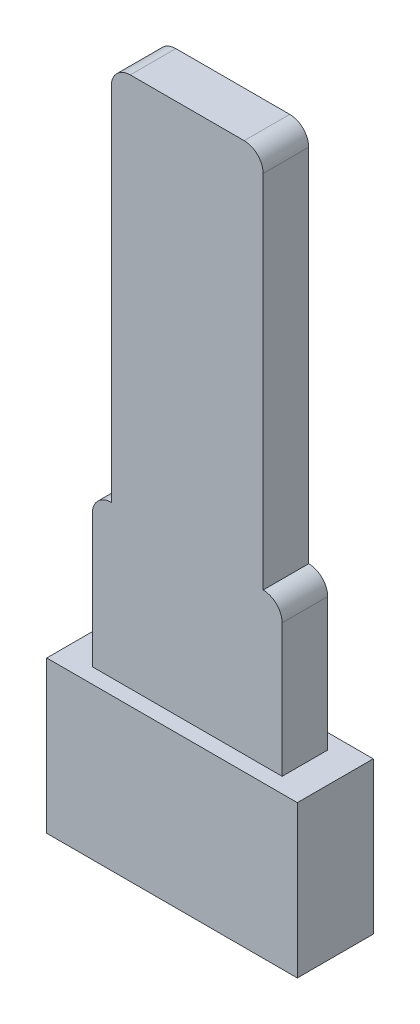
SolidWorks part; units mm, degrees
ref_plane "Front Plane" through (0, 0, 0) normal (0, 0, 1) x (1, 0, 0)
ref_plane "Top Plane" through (0, 0, 0) normal (0, 1, 0) x (1, 0, 0)
ref_plane "Right Plane" through (0, 0, 0) normal (1, 0, 0) x (0, 0, -1)
sketch "Sketch2" plane through (0, 0, 0) normal (0, 1, 0) x (1, 0, 0)
  line L1 (-3.3, -1) -> (3.3, -1)
  line L2 (-3.3, -1) -> (-3.3, 1)
  line L3 (-3.3, 1) -> (3.3, 1)
  line L4 (3.3, -1) -> (3.3, 1)
  line L5 (-3.3, -1) -> (3.3, 1) construction
  line L6 (-3.3, 1) -> (3.3, -1) construction
  point P0 (0, 0)
  dimension "D1" = 2
  dimension "D2" = 6.6
extrude "Boss-Extrude1" add sketch "Sketch2" along normal blind 4
sketch "Sketch3" plane through (0, 4, 0) normal (0, 1, 0) x (1, 0, 0)
  line L1 (-2.5, -0.6) -> (2.5, -0.6)
  line L2 (-2.5, -0.6) -> (-2.5, 0.6)
  line L3 (-2.5, 0.6) -> (2.5, 0.6)
  line L4 (2.5, -0.6) -> (2.5, 0.6)
  line L5 (-2.5, -0.6) -> (2.5, 0.6) construction
  line L6 (-2.5, 0.6) -> (2.5, -0.6) construction
  point P0 (0, 0)
  dimension "D1" = 5
  dimension "D2" = 1.2
extrude "Boss-Extrude2" add sketch "Sketch3" along normal blind 4
sketch "Sketch4" plane through (0, 8, 0) normal (0, 1, 0) x (1, 0, 0)
  line L1 (-2, -0.6) -> (2, -0.6)
  line L2 (-2, -0.6) -> (-2, 0.6)
  line L3 (-2, 0.6) -> (2, 0.6)
  line L4 (2, -0.6) -> (2, 0.6)
  line L5 (-2, -0.6) -> (2, 0.6) construction
  line L6 (-2, 0.6) -> (2, -0.6) construction
  point P0 (0, 0)
  dimension "D1" = 4
  dimension "D2" = 1.2
extrude "Boss-Extrude3" add sketch "Sketch4" along normal blind 10
fillet "Fillet3" radius 0.5 4 edges at (2.5, 8, 0) (-2.5, 8, 0) (2, 18, 0) (-2, 18, 0)
